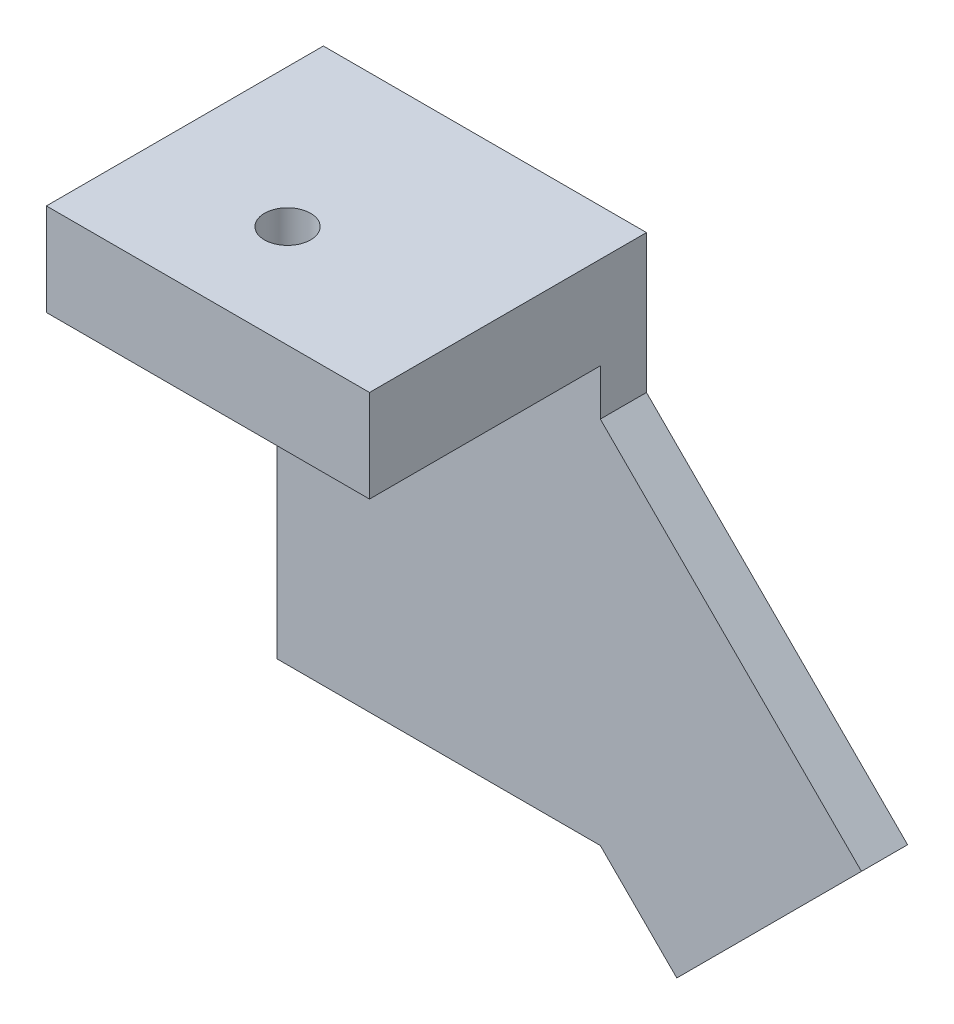
SolidWorks part; units mm, degrees
ref_plane "Front Plane" through (0, 0, 0) normal (0, 0, 1) x (1, 0, 0)
ref_plane "Top Plane" through (0, 0, 0) normal (0, 1, 0) x (1, 0, 0)
ref_plane "Right Plane" through (0, 0, 0) normal (1, 0, 0) x (0, 0, -1)
sketch "Sketch1" plane through (0, 0, 0) normal (0, 0, 1) x (1, 0, 0)
  line L0 (17.5, 27.5) -> (17.5, 12.5)
  line L5 (-17.5, 27.5) -> (17.5, 27.5)
  line L6 (-17.5, 27.5) -> (-17.5, -27.5)
  line L7 (-17.5, -27.5) -> (17.5, -27.5)
  line L9 (17.5, 12.5) -> (45.7843, -15.7843)
  line L10 (-17.5, -27.5) -> (17.5, 27.5) construction
  line L11 (45.7843, -15.7843) -> (25.7843, -35.7843)
  line L12 (25.7843, -35.7843) -> (17.5, -27.5)
  point P0 (0, 0)
  point P9 (17.5, -28.1877)
  point P10 (17.5, 7.4391)
  point P11 (23.2453, -38.3232)
  point P12 (0, 0)
  dimension "D1" = 45
  dimension "D2" = 55
  dimension "D3" = 35
  dimension "D4" = 40
  dimension "D5" = 15
extrude "Boss-Extrude1" add sketch "Sketch1" along normal blind 5
sketch "Sketch3" plane through (0, 0, 5) normal (0, 0, 1) x (1, 0, 0)
  line L0 (17.5, 12.5) -> (17.5, 27.5) construction
  line L1 (-17.5, 27.5) -> (17.5, 27.5)
  line L2 (-17.5, 27.5) -> (-17.5, 17.5)
  line L3 (-17.5, 17.5) -> (17.5, 17.5)
  line L4 (17.5, 27.5) -> (17.5, 17.5)
  dimension "D1" = 10
extrude "Boss-Extrude2" add sketch "Sketch3" along normal blind 25
sketch "Sketch4" plane through (0, 27.5, 0) normal (0, 1, 0) x (1, 0, 0)
  line L0 (-17.5, -30) -> (-17.5, 0) construction
  line L1 (17.5, -30) -> (-17.5, -30) construction
  line L2 (17.5, -30) -> (17.5, -5) construction
  line L3 (17.5, -5) -> (-17.5, -5) construction
  line L4 (-17.5, -30) -> (-17.5, -5) construction
  line L5 (17.5, -30) -> (17.5, 0) construction
  line L6 (-17.5, 0) -> (17.5, 0) construction
  line L7 (-17.5, 0) -> (-17.5, 5) construction
  line L8 (-17.5, 5) -> (17.5, 5) construction
  line L9 (17.5, 0) -> (17.5, 5) construction
  circle A0 centre (-2.5, -18.88) radius 2.5
  circle A1 centre (-2.5, -18.88) radius 6.5 construction
  dimension "D3" = 13
  dimension "D4" = 5
  dimension "D1" = 25
  dimension "D2" = 5
  dimension "D5" = 23.88
  dimension "D6" = 20
extrude "Cut-Extrude1" cut sketch "Sketch4" against normal through all
sketch "Sketch6" plane through (-17.5, 0, 0) normal (-1, 0, 0) x (0, 0, 1)
  line L0 (30, 17.5) -> (5, -7.3701)
  line L1 (5, 17.5) -> (5, -27.5) construction
rib "Rib1" sketch "Sketch6" sketch "Sketch6" thickness 5 extrusion direction parallel to sketch draft on no parameters "D1"=5
sketch "Sketch7" plane through (0, 0, 5) normal (0, 0, 1) x (1, 0, 0)
  line L0 (25.7843, -35.7843) -> (45.7843, -15.7843) construction
  line L1 (45.7843, -15.7843) -> (17.5, 12.5) construction
  circle A0 centre (17.5, -15.7843) radius 12.5
  point P4 (14.348, -18.9362)
  dimension "D1" = 20
  dimension "D3" = 25
  dimension "D2" = 20
